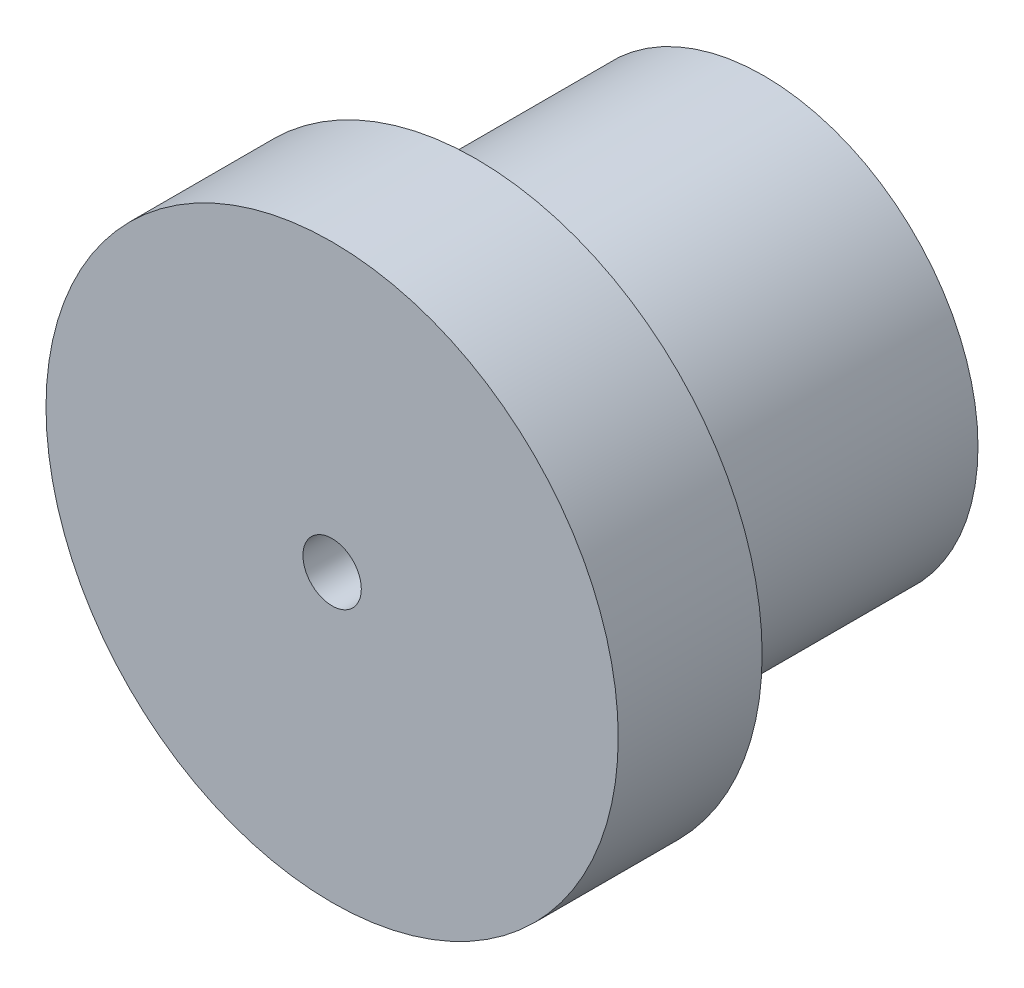
SolidWorks part; units mm, degrees
ref_plane "Front" through (0, 0, 0) normal (0, 0, 1) x (1, 0, 0)
ref_plane "Top" through (0, 0, 0) normal (0, 1, 0) x (1, 0, 0)
ref_plane "Right" through (0, 0, 0) normal (1, 0, 0) x (0, 0, -1)
sketch "Sketch1" plane through (0, 0, 0) normal (0, 0, 1) x (1, 0, 0)
  circle A0 centre (0, 0) radius 25.25
  circle A3 centre (0, 0) radius 25.4 construction
  point P2 (0, 0)
  dimension "D1" = 50.8
  dimension "D2" = 0.15
extrude "Boss-Extrude1" add sketch "Sketch1" against normal up to surface (12.7 mm away)
sketch "Sketch2" plane through (0, 0, -12.7) normal (0, 0, -1) x (-1, 0, 0)
  circle A0 centre (0, 0) radius 18.9
  circle A3 centre (0, 0) radius 19.05 construction
  dimension "D1" = 38.1
  dimension "D2" = 0.15
extrude "Boss-Extrude2" add sketch "Sketch2" along normal up to surface (25.4 mm away)
sketch "Sketch3" plane through (0, 0, -38.1) normal (0, 0, -1) x (-1, 0, 0)
  circle A0 centre (0, 0) radius 4.5
  dimension "D1" = 9
extrude "Cut-Extrude1" cut sketch "Sketch3" against normal blind 13
sketch "Sketch4" plane through (0, 0, 0) normal (0, 0, 1) x (1, 0, 0)
  line L0 (-2.24, 1.27) -> (2.24, 1.27)
  arc A0 (-2.24, 1.27) -> (2.24, 1.27) centre (0, 0) ccw
  arc A1 (2.24, 1.27) -> (-2.24, 1.27) centre (0, 0) ccw construction
  point P4 (0, 0)
  dimension "D1" = 5.15
  dimension "D2" = 4.48
extrude "Cut-Extrude2" cut sketch "Sketch4" against normal blind 20
sketch "Sketch5" plane through (0, 0, 0) normal (0, 0, 1) x (1, 0, 0)
  circle A0 centre (0, 0) radius 2.575
  dimension "D1" = 5.15
extrude "Cut-Extrude3" cut sketch "Sketch5" against normal blind 5
